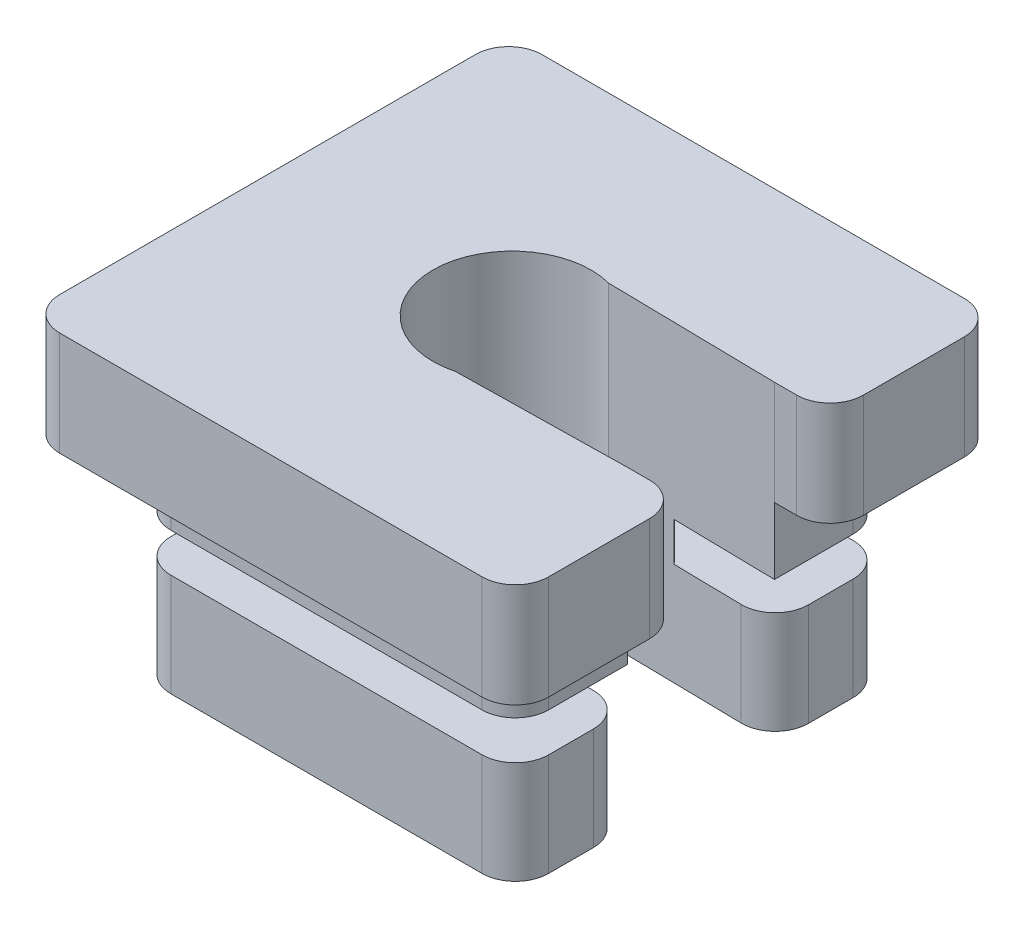
SolidWorks part; units mm, degrees
ref_plane "Front Plane" through (0, 0, 0) normal (0, 0, 1) x (1, 0, 0)
ref_plane "Top Plane" through (0, 0, 0) normal (0, 1, 0) x (1, 0, 0)
ref_plane "Right Plane" through (0, 0, 0) normal (1, 0, 0) x (0, 0, -1)
sketch "Sketch1" plane through (0, 0, 0) normal (0, 1, 0) x (1, 0, 0)
  line L0 (8.89, 5.9309) -> (14.3679, 5.9309)
  line L1 (8.89, -8.7376) -> (-8.89, -8.7376)
  line L2 (8.89, -8.7376) -> (8.89, 8.7376)
  line L3 (8.89, 8.7376) -> (-8.89, 8.7376)
  line L4 (-8.89, -8.7376) -> (-8.89, 8.7376)
  line L5 (8.89, -8.7376) -> (-8.89, 8.7376) construction
  line L6 (8.89, 8.7376) -> (-8.89, -8.7376) construction
  line L7 (0, 0) -> (14.3679, 0) construction
  line L8 (8.89, -5.9309) -> (14.3679, -5.9309)
  circle A0 centre (0, 0) radius 3.6195
  dimension "D1" = 7.239
  dimension "D2" = 17.4752
  dimension "D3" = 17.78
  dimension "D4" = 11.8618
sketch "Sketch2" plane through (0, 0, 0) normal (0, 1, 0) x (1, 0, 0)
  line L0 (8.89, -5.9309) -> (14.3679, -5.9309) construction
  line L1 (8.89, 5.9309) -> (14.3679, 5.9309) construction
  line L2 (8.89, -5.9309) -> (14.3679, -5.9309) construction
  line L3 (8.89, 5.9309) -> (14.3679, 5.9309) construction
  line L4 (-8.89, -8.7376) -> (8.89, -8.7376)
  line L5 (-8.89, 8.7376) -> (-8.89, -8.7376)
  line L6 (8.89, 8.7376) -> (-8.89, 8.7376)
  line L7 (8.89, -8.7376) -> (8.89, 8.7376)
  line L8 (-8.89, -8.7376) -> (8.89, -8.7376) construction
  line L9 (-8.89, 8.7376) -> (-8.89, -8.7376) construction
  line L10 (8.89, 8.7376) -> (-8.89, 8.7376) construction
  line L11 (8.89, -8.7376) -> (8.89, 8.7376) construction
  line L12 (8.64, 8.4876) -> (-8.64, 8.4876)
  line L13 (-8.64, 8.4876) -> (-8.64, -8.4876)
  line L14 (-8.64, -8.4876) -> (8.64, -8.4876)
  line L15 (8.64, -8.4876) -> (8.64, -3.3655)
  line L16 (0.9215, 3.5002) -> (8.64, 3.3655)
  line L17 (0, 0) -> (14.3679, 0) construction
  line L18 (0, 0) -> (14.3679, 0) construction
  line L19 (0.9215, -3.5002) -> (8.64, -3.3655)
  line L20 (8.64, 3.3655) -> (8.64, 8.4876)
  line L22 (8.64, -8.4876) -> (8.64, 8.4876) construction
  circle A1 centre (0, 0) radius 3.6195
  arc A2 (0.9215, 3.5002) -> (0.9215, -3.5002) centre (0, 0) ccw
  circle A3 centre (0, 0) radius 3.6195 construction
  dimension "D5" = 7.239
  dimension "D4" = 1
  dimension "D6" = 6.731
  dimension "D1" = 0
  dimension "D2" = 0
  dimension "D3" = 0.25
extrude "Boss-Extrude1" add sketch "Sketch2" along normal blind 9.525
sketch "Sketch3" plane through (0, 9.525, 0) normal (0, 1, 0) x (1, 0, 0)
  line L0 (11.18, 3.3655) -> (11.18, 11.0276)
  line L1 (11.18, 11.0276) -> (-11.18, 11.0276)
  line L2 (-11.18, 11.0276) -> (-11.18, -11.0276)
  line L3 (-11.18, -11.0276) -> (11.18, -11.0276)
  line L4 (11.18, -11.0276) -> (11.18, -3.3655)
  line L5 (8.64, 3.3655) -> (11.18, 3.3655)
  line L6 (8.64, -3.3655) -> (11.18, -3.3655)
  line L7 (8.64, 3.3655) -> (8.64, 8.4876)
  line L8 (8.64, 8.4876) -> (-8.64, 8.4876)
  line L9 (-8.64, 8.4876) -> (-8.64, -8.4876)
  line L10 (-8.64, -8.4876) -> (8.64, -8.4876)
  line L11 (8.64, -8.4876) -> (8.64, -3.3655)
  line L12 (8.64, -3.3655) -> (0.9215, -3.5002)
  line L13 (0.9215, 3.5002) -> (8.64, 3.3655)
  line L14 (8.64, 3.3655) -> (8.64, 8.4876) construction
  line L15 (8.64, 8.4876) -> (-8.64, 8.4876) construction
  line L16 (-8.64, 8.4876) -> (-8.64, -8.4876) construction
  line L17 (-8.64, -8.4876) -> (8.64, -8.4876) construction
  line L18 (8.64, -8.4876) -> (8.64, -3.3655) construction
  line L19 (8.64, -3.3655) -> (0.9215, -3.5002)
  line L20 (0.9215, 3.5002) -> (8.64, 3.3655)
  arc A1 (0.9215, 3.5002) -> (0.9215, -3.5002) centre (0, 0) ccw
  arc A2 (0.9215, 3.5002) -> (0.9215, -3.5002) centre (0, 0) ccw
  dimension "D1" = 0
  dimension "D2" = 2.54
extrude "Boss-Extrude2" add sketch "Sketch3" along normal blind 4.7625
ref_plane "Plane1" through (0, 6.477, 0) normal (0, -1, 0) x (-1, 0, 0)
sketch "Sketch4" plane through (0, 6.477, 0) normal (0, -1, 0) x (-1, 0, 0)
  line L7 (-8.64, 8.4876) -> (-8.64, 3.3655)
  line L8 (-8.64, 3.3655) -> (-0.9215, 3.5002)
  line L9 (-0.9215, -3.5002) -> (-8.64, -3.3655)
  line L10 (-8.64, -3.3655) -> (-8.64, -8.4876)
  line L11 (-8.64, -8.4876) -> (8.64, -8.4876)
  line L12 (8.64, -8.4876) -> (8.64, 8.4876)
  line L13 (8.64, 8.4876) -> (-8.64, 8.4876)
  line L14 (-8.64, 8.4876) -> (-8.64, 3.3655)
  line L15 (-8.64, 3.3655) -> (-3.9702, 3.447)
  line L16 (-3.9702, -3.447) -> (-8.64, -3.3655)
  line L17 (-8.64, -3.3655) -> (-8.64, -8.4876)
  line L18 (-8.64, -8.4876) -> (8.64, -8.4876)
  line L19 (8.64, -8.4876) -> (8.64, 8.4876)
  line L20 (8.64, 8.4876) -> (-8.64, 8.4876)
  arc A0 (-3.9702, -3.447) -> (-3.9702, 3.447) centre (0, 0) ccw
  arc A2 (-0.9215, -3.5002) -> (-0.9215, 3.5002) centre (0, 0) ccw
  dimension "D2" = 10.5156
  dimension "D1" = 0
extrude "Cut-Extrude1" cut sketch "Sketch4" along normal blind 1.778
fillet "Fillet1" radius 1.524 16 edges at (-11.18, 11.9062, 11.0276) (-8.64, 8.001, 8.4876) (8.64, 8.001, -8.4876) (8.64, 8.001, 8.4876) (11.18, 11.9062, 11.0276) (11.18, 11.9062, -11.0276) (-11.18, 11.9062, -11.0276) (-8.64, 8.001, -8.4876) (-8.64, 2.3495, -8.4876) (8.64, 2.3495, -8.4876) (-8.64, 2.3495, 8.4876) (8.64, 2.3495, 8.4876) (8.64, 2.3495, -3.3655) (8.64, 2.3495, 3.3655) (11.18, 11.9062, -3.3655) (11.18, 11.9062, 3.3655)
